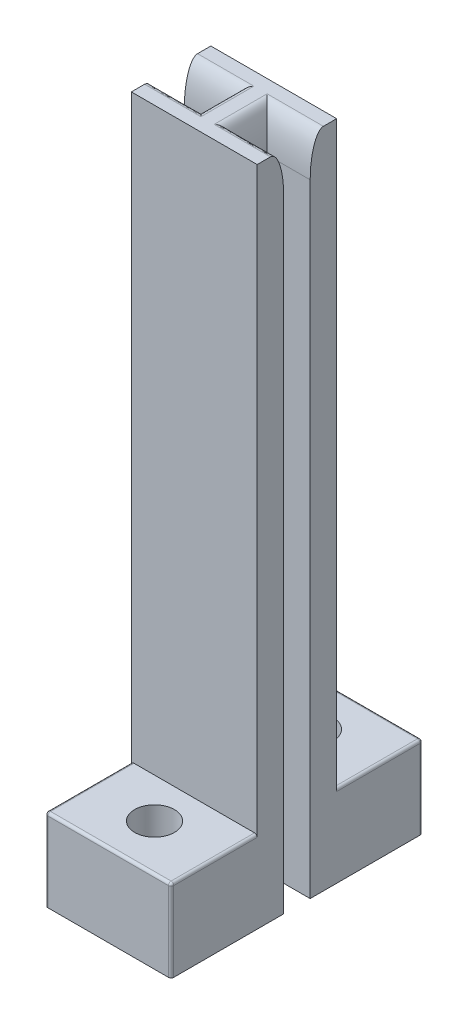
SolidWorks part; units mm, degrees
note: The reader was unsure of these and kept them because the rebuilt part matched: shared geometry of "Sketch1<3>".
ref_plane "Front Plane" through (0, 0, 0) normal (0, 0, 1) x (1, 0, 0)
ref_plane "Top Plane" through (0, 0, 0) normal (0, 1, 0) x (1, 0, 0)
ref_plane "Right Plane" through (0, 0, 0) normal (1, 0, 0) x (0, 0, -1)
sketch "Sketch1" plane through (0, 0, 0) normal (0, 1, 0) x (1, 0, 0)
  line L0 (0, 0) -> (0, 8.5)
  line L1 (0, 8.5) -> (3.25, 8.5)
  line L2 (3.25, 8.5) -> (3.25, 10.5)
  line L3 (3.25, 10.5) -> (0, 10.5)
  line L4 (0, 10.5) -> (0, 19)
  line L5 (0, 19) -> (9.5, 19)
  line L6 (9.5, 19) -> (9.5, 10.5)
  line L7 (9.5, 10.5) -> (6.25, 10.5)
  line L8 (6.25, 10.5) -> (6.25, 8.5)
  line L9 (6.25, 8.5) -> (9.5, 8.5)
  line L10 (9.5, 8.5) -> (9.5, 0)
  line L11 (9.5, 0) -> (0, 0)
  line L12 (0, 0) -> (0.3184, -0.0398)
  line L13 (0, 6.5) -> (9.5, 6.5)
  line L14 (0, 12.5) -> (9.5, 12.5)
  circle A0 centre (4.75, 15.5) radius 1.5
  circle A1 centre (4.75, 3.5) radius 1.5
  point P3 (1.625, 10.5)
  point P15 (6.25, 9.5)
  point P22 (4.75, 12.5)
  point P25 (0, 0)
  point P26 (0, 0)
  dimension "D17" = 3
  dimension "D19" = 3
  dimension "D1" = 8.5
  dimension "D2" = 10.5
  dimension "D3" = 19
  dimension "D4" = 8.5
  dimension "D5" = 2
  dimension "D6" = 9.5
  dimension "D7" = 3.25
  dimension "D8" = 6.25
  dimension "D9" = 3
  dimension "D10" = 3.25
  dimension "D11" = 6
  dimension "D12" = 6.5
  dimension "D13" = 2
  dimension "D14" = 2
  dimension "D15" = 2
  dimension "D16" = 4.75
  dimension "D18" = 3
extrude "Boss-Extrude1" add sketch "Sketch1" along normal blind 6.2 contours L13 L0 L11 L10 A1 | L4 L14 L6 L5 A0
extrude "Boss-Extrude2" add sketch "Sketch1<3>" along normal blind 50 contours L14 L4 L3 L2 L1 L0 L13 L10 L9 L8 L7 L6
sketch "Sketch1<3>" plane through (0, 0, 0) normal (0, 1, 0) x (1, 0, 0) same geometry as "Sketch1"
fillet "Fillet7" radius 1 4 edges at (1.625, 50, -8.5) (1.625, 50, -10.5) (7.875, 50, -8.5) (7.875, 50, -10.5)
fillet "Fillet8" radius 1 2 edges
fillet "Fillet9" radius 0.2 10 edges at (0, 3.1, 0) (0, 6.2, -3.25) (9.5, 3.1, 0) (4.75, 6.2, 0) (9.5, 6.2, -3.25) (0, 6.2, -15.75) (0, 3.1, -19) (9.5, 3.1, -19) (4.75, 6.2, -19) (9.5, 6.2, -15.75)
